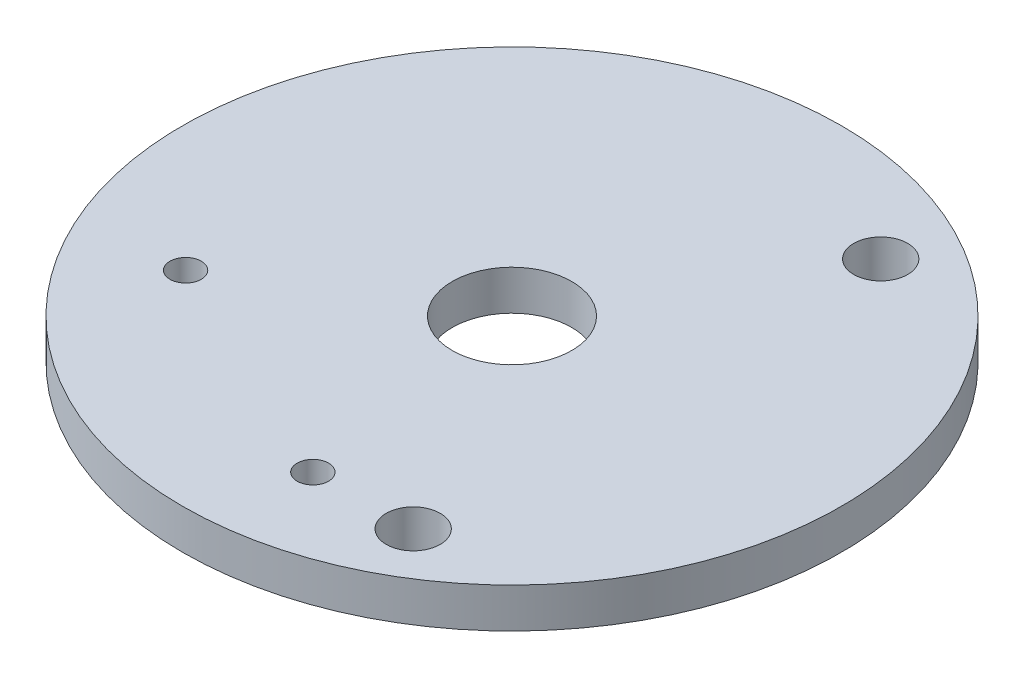
SolidWorks part; units mm, degrees
material "6061 Alloy"
ref_plane "Front Plane" through (0, 0, 0) normal (0, 0, 1) x (1, 0, 0)
ref_plane "Top Plane" through (0, 0, 0) normal (0, 1, 0) x (1, 0, 0)
ref_plane "Right Plane" through (0, 0, 0) normal (1, 0, 0) x (0, 0, -1)
sketch "Sketch1" plane through (0, 0, 0) normal (0, 1, 0) x (1, 0, 0)
  line L1 (-26.25, 26.25) -> (26.25, 26.25) construction
  line L2 (-26.25, 26.25) -> (-26.25, -38.75) construction
  line L3 (-26.25, -38.75) -> (26.25, -38.75) construction
  line L4 (26.25, 26.25) -> (26.25, -38.75) construction
  line L5 (-26.25, 26.25) -> (26.25, -38.75) construction
  line L6 (-26.25, -38.75) -> (26.25, 26.25) construction
  circle A2 centre (0, 0) radius 4.7625
  circle A3 centre (0, 0) radius 26.25
  point P4 (0, -6.25)
  dimension "D5" = 52.5
  dimension "D6" = 9.525
  dimension "D2" = 65
extrude "Boss-Extrude1" add sketch "Sketch1" along normal mid plane 3.175 contours L4 A3 L1 L2 L3 | A3 A2 region at (-25.5075, 0, 0)
hole_wizard "M4 Clearance Hole1" positions "Sketch6" profile "Sketch7" hole size "M4" standard "ANSI Metric" end condition up to next
sketch "Sketch6" plane through (0, 1.5875, 0) normal (0, 1, 0) x (1, 0, 0)
  line L0 (0, 0) -> (10.75, 18.6195)
  line L1 (0, 0) -> (10.75, -18.6195)
  line L2 (0, 0) -> (-21.5, 0)
  point P2 (10.75, 18.6195)
  point P10 (10.75, -18.6195)
  dimension "D1" = 21.5
  dimension "D2" = 120
  dimension "D3" = 120
sketch "Sketch7" plane through (10.75, 1.5875, 18.6195) normal (1, 0, 0) x (0, 0, 1)
  line L0 (0, 0) -> (0, 3.175)
  line L1 (0, 3.175) -> (2.15, 3.175)
  line L2 (2.15, 3.175) -> (2.15, 0)
  line L5 (2.15, 0) -> (0, 0)
  line L11 (0, -6.35) -> (0, 107.95) construction
  dimension "Thru Hole Dia." = 4.3
  dimension "Thru Hole Depth" = 3.175
hole_wizard "M3x0.5 Tapped Hole1" positions "Sketch8" profile "Sketch9" tap size "M3x0.5" standard "ANSI Metric" end condition up to next
sketch "Sketch8" plane through (0, 1.5875, 0) normal (0, 1, 0) x (1, 0, 0)
  line L2 (-1000, 0) -> (49000, 0) construction
  line L3 (0, 0) -> (-6.6562, -14.2743) construction
  line L5 (-16.1543, -9.8453) -> (2.8419, -18.7034) construction
  point P20 (0, 0)
  point P47 (-16.1543, -9.8453)
  point P50 (2.8419, -18.7034)
  dimension "D1" = 15.75
  dimension "D2" = 25
  dimension "D3" = 20.96
sketch "Sketch9" plane through (0, 1.5875, 0) normal (1, 0, 0) x (0, 0, 1)
  line L0 (0, 0) -> (0, 3.175)
  line L1 (0, 3.175) -> (1.25, 3.175)
  line L2 (1.25, 3.175) -> (1.25, 0)
  line L5 (1.25, 0) -> (0, 0)
  line L11 (0, -6.35) -> (0, 107.95) construction
  dimension "Thru Tap Drill Dia." = 2.5
  dimension "Thru Tap Drill Depth" = 3.175
cosmetic thread "Hole Thread1" parameters "D2"=3
cosmetic thread "Hole Thread6" parameters "D2"=3
